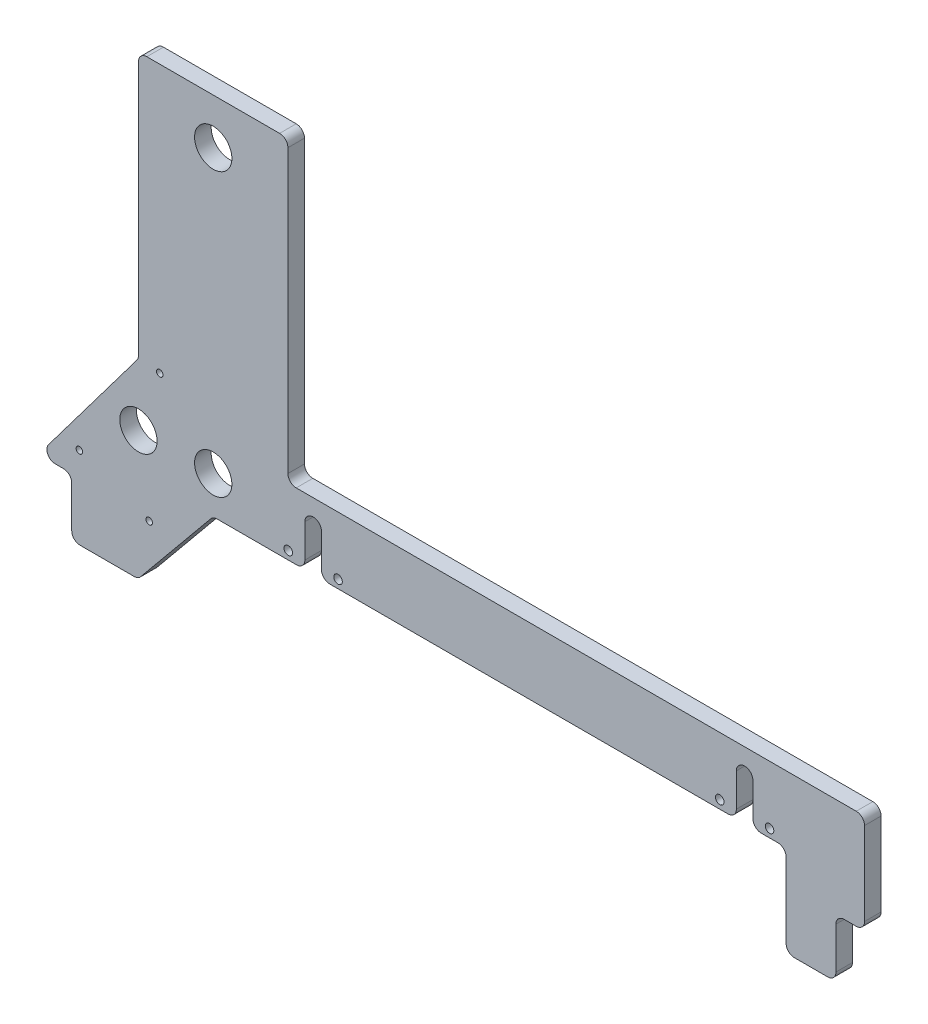
SolidWorks part; units mm, degrees
material "6061 Alloy"
ref_plane "Front Plane" through (0, 0, 0) normal (0, 0, 1) x (1, 0, 0)
ref_plane "Top Plane" through (0, 0, 0) normal (0, 1, 0) x (1, 0, 0)
ref_plane "Right Plane" through (0, 0, 0) normal (1, 0, 0) x (0, 0, -1)
sketch "Sketch1" plane through (0, 0, 0) normal (0, 0, 1) x (1, 0, 0)
  line L0 (-247.3346, 114.3762) -> (-247.3346, -165.1) construction
  line L1 (-190.1846, 114.3762) -> (-304.4846, 114.3762)
  line L2 (-355.6, -234.95) -> (-355.6, -190.5)
  line L3 (165.6792, -165.1) -> (191.0792, -165.1)
  line L4 (-190.1846, -88.8238) -> (-190.1846, 114.3762)
  line L5 (-164.5208, -165.1) -> (152.9792, -165.1)
  line L6 (-247.3346, -165.1) -> (-177.2208, -165.1)
  line L7 (-304.4846, 114.3762) -> (-304.4846, -88.8238)
  line L8 (-177.2208, -165.1) -> (-177.2208, -127)
  line L9 (-304.4846, -88.8238) -> (-381, -190.5)
  line L10 (251.0648, -88.8238) -> (-190.1846, -88.8238) construction
  line L11 (-304.4846, -88.8238) -> (-251.6638, -88.8238) construction
  line L12 (-355.6, -190.5) -> (-381, -190.5)
  line L13 (-247.3346, -136.4488) -> (-421.4784, -136.4488) construction
  line L14 (-355.6, -234.95) -> (-304.8, -234.95)
  line L15 (-177.2208, -127) -> (-164.5208, -127)
  line L16 (-251.6638, -88.8238) -> (-251.6638, -113.6796) construction
  line L17 (251.0648, -88.8238) -> (251.0648, -190.5) construction
  line L18 (-164.5208, -165.1) -> (-164.5208, -127)
  line L19 (-304.4846, -88.8238) -> (-297.3281, -88.8238) construction
  line L20 (-304.8, -234.95) -> (-247.3346, -165.1)
  line L21 (152.9792, -127) -> (165.6792, -127)
  line L22 (152.9792, -127) -> (152.9792, -165.1)
  line L23 (-297.3281, -88.8238) -> (-297.3281, -79.3155) construction
  line L24 (165.6792, -127) -> (165.6792, -165.1)
  line L25 (229.1775, -234.95) -> (191.0792, -234.95)
  line L26 (-190.1846, -88.8238) -> (-190.1846, -114.2238)
  line L27 (-381, -190.5) -> (-333.5795, -190.5) construction
  line L28 (191.0792, -165.1) -> (191.0792, -234.95)
  line L29 (-333.5795, -190.5) -> (-333.5795, -175.0097) construction
  line L30 (-190.1846, -114.2238) -> (251.0648, -114.2238)
  line L31 (251.0648, -190.5) -> (229.1775, -190.5)
  line L32 (229.1775, -234.95) -> (229.1775, -190.5)
  line L33 (251.0648, -114.2238) -> (251.0648, -190.5)
  circle A0 centre (-247.3346, 79.4512) radius 14.2748
  circle A1 centre (-247.3346, -136.4488) radius 14.2748
  circle A2 centre (-247.3346, -136.4488) radius 45.72 construction
  circle A3 centre (-304.5608, -136.4488) radius 11.43 construction
  circle A4 centre (-304.5608, -136.4488) radius 14.2748
  point P5 (-247.3346, -136.4488)
  point P39 (-304.5608, -136.4488)
  dimension "D11" = 28.5496
  dimension "D17" = 25.4
  dimension "D18" = 91.44
  dimension "D20" = 22.86
  dimension "D21" = 28.5496
  dimension "D25" = 38.1762
  dimension "D5" = 28.5496
  dimension "D4" = 25.4
  dimension "D6" = 76.8204
  dimension "D7" = 44.45
  dimension "D8" = 317.5
  dimension "D9" = 12.7
  dimension "D10" = 441.2495
  dimension "D12" = 44.45
  dimension "D13" = 38.0983
  dimension "D14" = 38.1
  dimension "D15" = 203.2
  dimension "D16" = 215.9
  dimension "D19" = 57.2262
  dimension "D22" = 114.3
  dimension "D23" = 58.2719
  dimension "D24" = 15.4903
  dimension "D26" = 22.0205
  dimension "D27" = 103.9362
  dimension "D29" = 50.8
  dimension "D31" = 101.6762
  dimension "D32" = 21.8873
  dimension "D33" = 127.2503
extrude "Boss-Extrude1" add sketch "Sketch1" along normal mid plane 12.7 contours L6 A0 | A0 L6 L8 L15 L18 L21 L24 L3 region at (-197.4064, 12.7762, 0)
sketch "Sketch2" plane through (0, 0, 6.35) normal (0, 0, 1) x (1, 0, 0)
  line L0 (-288.2268, -90.4473) -> (-349.758, -172.212) construction
  line L1 (-349.758, -172.212) -> (-296.3143, -192.4578) construction
  line L2 (-296.3143, -192.4578) -> (-288.2268, -90.4473) construction
  line L3 (-304.4846, -88.8238) -> (-381, -190.5) construction
  line L5 (-355.6, -190.5) -> (-381, -190.5) construction
  circle A0 centre (-288.2268, -90.4473) radius 2.4892
  circle A1 centre (-349.758, -172.212) radius 2.4892
  circle A2 centre (-296.3143, -192.4578) radius 2.4892
  dimension "D3" = 4.9784
  dimension "D6" = 18.288
  dimension "D4" = 102.3306
  dimension "D1" = 102.3306
  dimension "D2" = 57.15
  dimension "D5" = 31.242
extrude "Cut-Extrude1" cut sketch "Sketch2" against normal through all
fillet "Fillet1" radius 6.35 4 edges at (152.9792, -127, 0) (165.6792, -127, 0) (-164.5208, -127, 0) (-177.2208, -127, 0)
sketch "Sketch3" plane through (0, 0, 6.35) normal (0, 0, 1) x (1, 0, 0)
  line L0 (165.6792, -165.1) -> (191.0792, -165.1) construction
  line L1 (165.6792, -165.1) -> (191.0792, -165.1)
  line L2 (165.6792, -165.1) -> (165.6792, -152.4)
  line L3 (165.6792, -152.4) -> (191.0792, -152.4)
  line L4 (191.0792, -165.1) -> (191.0792, -152.4)
  line L5 (165.6792, -133.35) -> (165.6792, -165.1) construction
  line L6 (191.0792, -158.75) -> (178.3792, -158.75) construction
  line L7 (165.6792, -158.75) -> (178.3792, -158.75) construction
  line L8 (-164.5208, -165.1) -> (152.9792, -165.1) construction
  line L9 (-5.7708, -64.7008) -> (-5.7708, -232.2239) construction
  line L10 (-177.2208, -158.75) -> (-189.9208, -158.75) construction
  line L11 (-202.6208, -158.75) -> (-189.9208, -158.75) construction
  line L12 (-202.6208, -165.1) -> (-202.6208, -152.4)
  line L13 (-177.2208, -152.4) -> (-202.6208, -152.4)
  line L14 (-177.2208, -165.1) -> (-177.2208, -152.4)
  line L15 (-177.2208, -165.1) -> (-202.6208, -165.1)
  line L16 (-164.5208, -165.1) -> (-164.5208, -133.35) construction
  line L17 (-164.5208, -152.4) -> (-139.1208, -152.4)
  line L18 (-164.5208, -152.4) -> (-164.5208, -165.1)
  line L19 (-164.5208, -165.1) -> (-139.1208, -165.1)
  line L20 (-139.1208, -152.4) -> (-139.1208, -165.1)
  line L21 (-139.1208, -158.75) -> (-151.8208, -158.75) construction
  line L22 (-164.5208, -158.75) -> (-151.8208, -158.75) construction
  line L23 (152.9792, -158.75) -> (140.2792, -158.75) construction
  line L24 (127.5792, -158.75) -> (140.2792, -158.75) construction
  line L25 (127.5792, -152.4) -> (127.5792, -165.1)
  line L26 (152.9792, -165.1) -> (127.5792, -165.1)
  line L27 (152.9792, -152.4) -> (152.9792, -165.1)
  line L28 (152.9792, -152.4) -> (127.5792, -152.4)
  circle A0 centre (178.3792, -158.75) radius 3.2639
  circle A1 centre (-189.9208, -158.75) radius 3.2639
  circle A2 centre (-151.8208, -158.75) radius 3.2639
  circle A3 centre (140.2792, -158.75) radius 3.2639
  point P12 (-5.7708, -165.1)
  dimension "D3" = 6.35
  dimension "D5" = 6.5278
  dimension "D1" = 25.4
  dimension "D2" = 12.7
  dimension "D4" = 25.4
extrude "Cut-Extrude2" cut sketch "Sketch3" against normal through all contours A1 | A0 | A2 | A3 region at (178.3792, -158.75, 6.35) region at (-189.9208, -158.75, 6.35) region at (-151.8208, -158.75, 6.35) region at (140.2792, -158.75, 6.35)
fillet "Fillet2" radius 6.35 19 edges at (-304.4846, -88.8238, 0) (-304.4846, 114.3762, 0) (-190.1846, 114.3762, 0) (-190.1846, -114.2238, 0) (251.0648, -114.2238, 0) (251.0648, -190.5, 0) (229.1775, -190.5, 0) (229.1775, -234.95, 0) (191.0792, -234.95, 0) (191.0792, -165.1, 0) (165.6792, -165.1, 0) (152.9792, -165.1, 0) (-164.5208, -165.1, 0) (-177.2208, -165.1, 0) (-247.3346, -165.1, 0) (-304.8, -234.95, 0) (-355.6, -234.95, 0) (-355.6, -190.5, 0) (-381, -190.5, 0)
